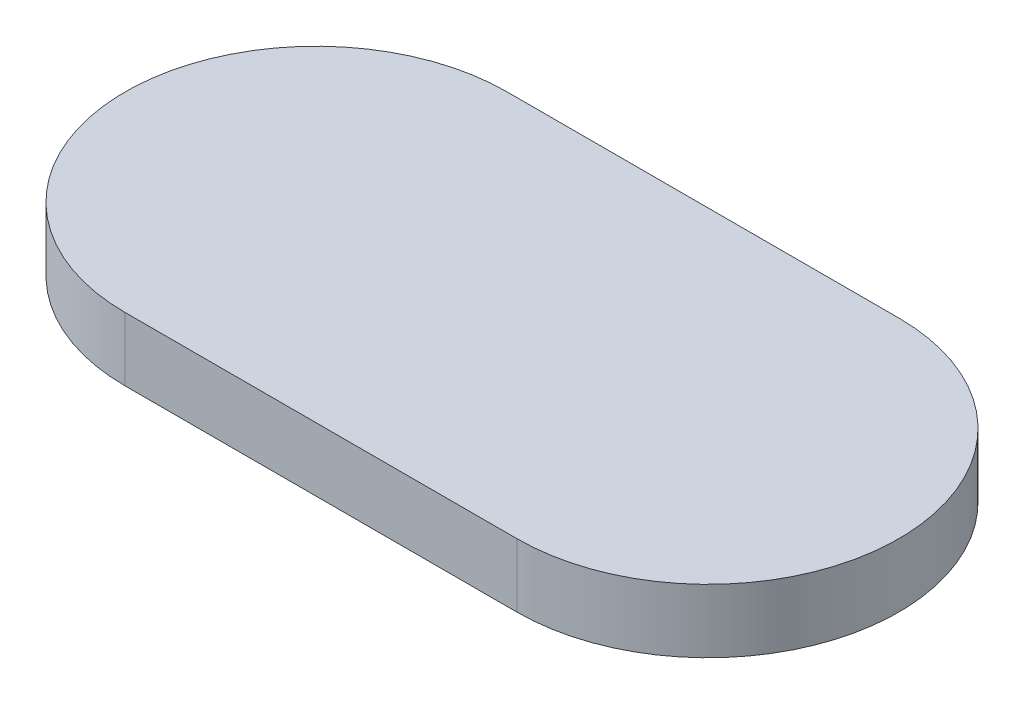
SolidWorks part; units mm, degrees
material "ABS"
ref_plane "Płaszczyzna przednia" through (0, 0, 0) normal (0, 0, 1) x (1, 0, 0)
ref_plane "Płaszczyzna górna" through (0, 0, 0) normal (0, 1, 0) x (1, 0, 0)
ref_plane "Płaszczyzna prawa" through (0, 0, 0) normal (1, 0, 0) x (0, 0, -1)
sketch "Szkic1" plane through (0, 0, 0) normal (0, 1, 0) x (1, 0, 0)
  line L0 (0, 0) -> (61.6043, 0) construction
  line L1 (0, 30.0321) -> (61.6043, 30.0321)
  line L2 (0, -30.0321) -> (61.6043, -30.0321)
  arc A0 (0, 30.0321) -> (0, -30.0321) centre (0, 0) ccw
  arc A1 (61.6043, -30.0321) -> (61.6043, 30.0321) centre (61.6043, 0) ccw
  point P3 (30.8021, 0)
extrude "Dodanie-wyciągnięcie1" add sketch "Szkic1" along normal blind 10
